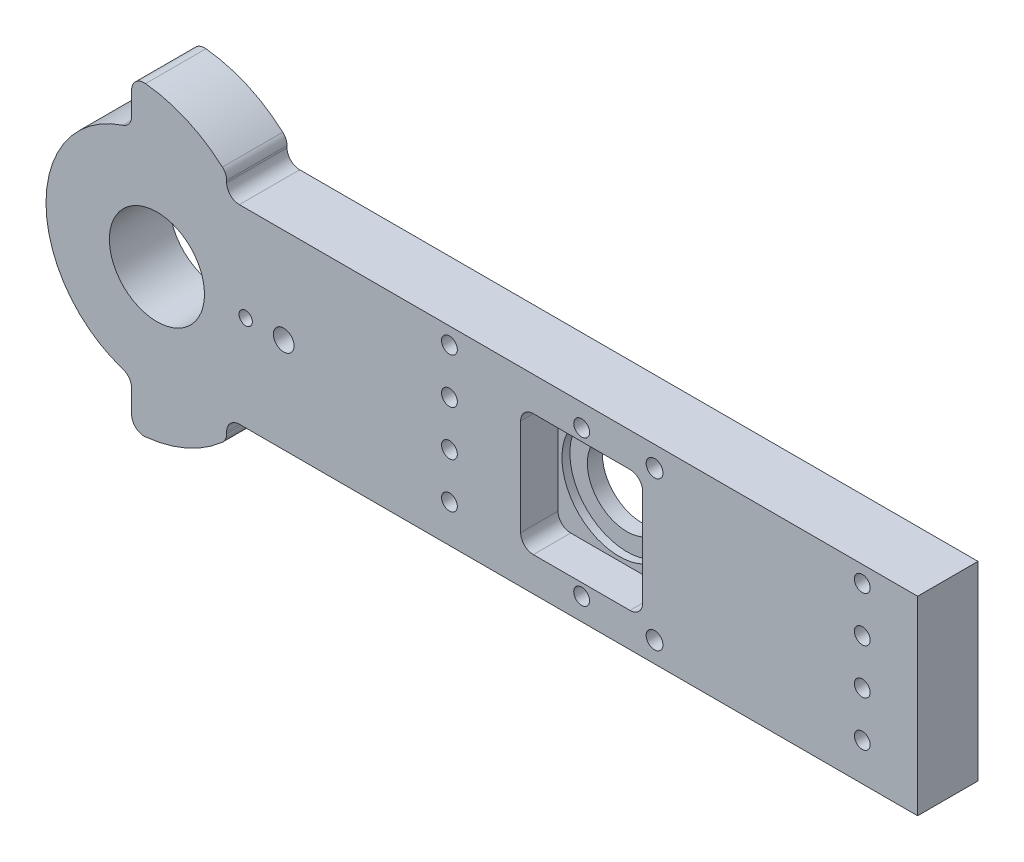
SolidWorks part; units mm, degrees
material "PE High Density"
ref_plane "Front Plane" through (0, 0, 0) normal (0, 0, 1) x (1, 0, 0)
ref_plane "Top Plane" through (0, 0, 0) normal (0, 1, 0) x (1, 0, 0)
ref_plane "Right Plane" through (0, 0, 0) normal (1, 0, 0) x (0, 0, -1)
sketch "Sketch1" plane through (0, 0, 0) normal (0, 0, 1) x (1, 0, 0)
  line L0 (30, 0) -> (30, 30) construction
  line L3 (0, 30) -> (18.0278, 30) construction
  line L6 (0, 0) -> (30, 0) construction
  line L8 (18.0278, 30) -> (240, 30)
  line L9 (240, 30) -> (240, -30)
  line L11 (18.0278, -30) -> (240, -30)
  circle A0 centre (0, 0) radius 30 construction
  arc A2 (18.0278, 30) -> (18.0278, -30) centre (0, 0) ccw
  circle A5 centre (0, 0) radius 9.525
  dimension "D1" = 60
  dimension "D4" = 70
  dimension "D8" = 19.05
  dimension "D2" = 240
extrude "Boss-Extrude1" add sketch "Sketch1" along normal mid plane 19.05
sketch "Sketch2" plane through (0, 0, -9.525) normal (0, 0, 1) x (1, 0, 0)
  line L0 (240, -30) -> (240, 30) construction
  circle A0 centre (134, 0) radius 12.5
  dimension "D2" = 25
  dimension "D1" = 106
extrude "Cut-Extrude1" cut sketch "Sketch2" along normal through all
sketch "Sketch3" plane through (0, 0, 9.525) normal (0, 0, 1) x (1, 0, 0)
  line L1 (114.5, -19.5) -> (153.5, -19.5) construction
  line L2 (114.5, -19.5) -> (114.5, 19.5) construction
  line L3 (114.5, 19.5) -> (153.5, 19.5) construction
  line L4 (153.5, -19.5) -> (153.5, 19.5) construction
  line L5 (114.5, -19.5) -> (153.5, 19.5) construction
  line L6 (114.5, 19.5) -> (153.5, -19.5) construction
  circle A0 centre (134, 0) radius 12.5 construction
  circle A3 centre (134, 0) radius 18
  dimension "D1" = 36
  dimension "D2" = 39
  dimension "D3" = 39
extrude "Cut-Extrude2" cut sketch "Sketch3" against normal blind 14.2875
sketch "Sketch4" plane through (0, 0, 9.525) normal (0, 0, 1) x (1, 0, 0)
  circle A0 centre (0, 0) radius 15
  dimension "D1" = 30
extrude "Cut-Extrude3" cut sketch "Sketch4" against normal through all
sketch "Sketch5" plane through (0, 0, 9.525) normal (0, 0, 1) x (1, 0, 0)
  line L1 (114.75, -19.25) -> (153.25, -19.25)
  line L2 (114.75, -19.25) -> (114.75, 19.25)
  line L3 (114.75, 19.25) -> (153.25, 19.25)
  line L4 (153.25, -19.25) -> (153.25, 19.25)
  line L5 (114.75, -19.25) -> (153.25, 19.25) construction
  line L6 (114.75, 19.25) -> (153.25, -19.25) construction
  point P0 (134, 0)
  dimension "D1" = 38.5
  dimension "D2" = 38.5
extrude "Cut-Extrude4" cut sketch "Sketch5" against normal offset from surface (11.7875 mm away) 2.5 up to face at (146.5, 0, -4.7625)
fillet "Fillet3" radius 4 4 edges at (153.25, -19.25, 3.6313) (114.75, -19.25, 3.6313) (153.25, 19.25, 3.6313) (114.75, 19.25, 3.6313)
sketch "Sketch12" plane through (0, 0, 9.525) normal (0, 0, 1) x (1, 0, 0)
  line L1 (240, 30) -> (18.0278, 30) construction
  line L3 (22, 30) -> (22, 36.35)
  line L4 (-8, 48.5) -> (22, 48.5) construction
  line L5 (-8, 48.5) -> (-8, 34.0735)
  line L6 (240, 30) -> (18.0278, 30) construction
  line L7 (22, 30) -> (18.0278, 30)
  arc A0 (-8, 48.5) -> (22, 36.35) centre (-8, 5.388) cw
  arc A1 (18.0278, 30) -> (18.0278, -30) centre (0, 0) ccw construction
  arc A2 (18.0278, 30) -> (-8, 34.0735) centre (0, 0) ccw
  dimension "D2" = 6.35
  dimension "D3" = 30
  dimension "D1" = 48.5
  dimension "D4" = 8
extrude "Boss-Extrude2" add sketch "Sketch12" against normal through all
mirror "Mirror4" about plane through (0, 0, 0) normal (0, 1, 0) of "Boss-Extrude2"
fillet "Fillet4" radius 4 6 edges at (22, 36.35, 0) (22, -36.35, 0) (-8, -48.5, 0) (-8, 48.5, 0) (-8, -34.0735, 0) (-8, 34.0735, 0)
fillet "Fillet6" radius 4 2 edges at (22, 30, 0) (22, -30, 0)
sketch "Sketch14" plane through (0, 0, 9.525) normal (0, 0, 1) x (1, 0, 0)
  line L0 (0, 0) -> (40, 0) construction
  line L1 (0, 0) -> (40, 0) construction
  circle A0 centre (0, 0) radius 40 construction
  circle A1 centre (40, 0) radius 3.2639
  dimension "D1" = 80
  dimension "D2" = 6.5278
  dimension "D3" = 0
extrude "Cut-Extrude6" cut sketch "Sketch14" against normal through all
sketch "Sketch15" plane through (0, 0, 9.525) normal (0, 0, 1) x (1, 0, 0)
  line L0 (134, 0) -> (134, 23) construction
  line L1 (240, 30) -> (26, 30) construction
  line L2 (134, 0) -> (146.5, 0) construction
  circle A0 centre (134, 0) radius 12.5 construction
  point P0 (134, 23)
  point P9 (134, -23)
  dimension "D1" = 7
hole_wizard "Ø5.0mm Dowel Hole1" positions "Sketch16" profile "Sketch17" hole size "Ø5.0" standard "ANSI Metric" end condition through all
sketch "Sketch16" plane through (0, 0, -9.525) normal (0, 0, -1) x (-1, 0, 0)
  point P0 (-134, 23)
  point P3 (-134, -23)
sketch "Sketch17" plane through (134, 23, -9.525) normal (1, 0, 0) x (0, 1, 0)
  line L0 (0, 0) -> (0, 19.05)
  line L1 (0, 19.05) -> (2.5, 19.05)
  line L2 (2.5, 19.05) -> (2.5, 0)
  line L5 (2.5, 0) -> (0, 0)
  line L11 (0, -6.35) -> (0, 107.95) construction
  dimension "Thru Hole Dia." = 5
  dimension "Thru Hole Depth" = 19.05
sketch "Sketch18" plane through (0, 0, 9.525) normal (0, 0, 1) x (1, 0, 0)
  line L0 (26, -30) -> (240, -30) construction
  line L1 (240, 30) -> (227.3, 30) construction
  line L2 (240, 30) -> (240, -30) construction
  line L3 (240, -30) -> (227.3, -30) construction
  line L4 (227.3, 30) -> (227.3, -30) construction
  line L5 (240, 30) -> (26, 30) construction
  line L6 (97.05, 30) -> (109.75, 30) construction
  line L7 (97.05, 30) -> (97.05, -30) construction
  line L8 (97.05, -30) -> (109.75, -30) construction
  line L9 (109.75, 30) -> (109.75, -30) construction
  line L10 (222.5375, 30) -> (222.5375, -30) construction
  line L11 (97.05, 30) -> (87.525, 30) construction
  line L12 (97.05, 30) -> (97.05, -30) construction
  line L13 (97.05, -30) -> (87.525, -30) construction
  line L14 (87.525, 30) -> (87.525, -30) construction
  line L15 (227.3, 30) -> (217.775, 30) construction
  line L16 (227.3, 30) -> (227.3, -30) construction
  line L17 (227.3, -30) -> (217.775, -30) construction
  line L18 (217.775, 30) -> (217.775, -30) construction
  line L19 (92.2875, 30) -> (92.2875, -30) construction
  line L20 (222.5375, -18.0938) -> (222.5375, -3.8063) construction
  point P21 (92.2875, -18.0938)
  point P22 (222.5375, -18.0938)
  point P24 (92.2875, -3.8063)
  point P25 (222.5375, -3.8063)
  point P26 (92.2875, 10.4812)
  point P27 (222.5375, 10.4812)
  point P28 (92.2875, 24.7687)
  point P29 (222.5375, 24.7687)
  dimension "D1" = 12.7
  dimension "D2" = 12.7
  dimension "D3" = 130.25
  dimension "D4" = 9.525
  dimension "D5" = 9.525
  dimension "D6" = 11.9062
  dimension "D8" = 14.2875
  dimension "D7" = 4
hole_wizard "CSK for #10 Flat Head Machine Screw1" positions "Sketch19" profile "Sketch20" countersink size "#10" standard "ANSI Inch" end condition up to next
sketch "Sketch19" plane through (0, 0, -9.525) normal (0, 0, -1) x (-1, 0, 0)
  point P0 (-92.2875, 24.7687)
  point P3 (-92.2875, 10.4812)
  point P6 (-92.2875, -3.8063)
  point P9 (-92.2875, -18.0938)
  point P12 (-222.5375, 24.7687)
  point P15 (-222.5375, 10.4812)
  point P18 (-222.5375, -3.8063)
  point P21 (-222.5375, -18.0938)
sketch "Sketch20" plane through (92.2875, 24.7687, -9.525) normal (1, 0, 0) x (0, 1, 0)
  line L0 (0, 0) -> (0, 19.05)
  line L1 (0, 19.05) -> (2.4892, 19.05)
  line L2 (2.4892, 19.05) -> (2.4892, 3.1265)
  line L3 (2.4892, 3.1265) -> (5.207, 0)
  line L5 (5.207, 0) -> (0, 0)
  line L6 (-2.4892, 3.1265) -> (-5.207, 0) construction
  line L11 (0, -6.35) -> (0, 107.95) construction
  dimension "Thru Hole Dia." = 4.9784
  dimension "Thru Hole Depth" = 19.05
  dimension "Near C'Sink Dia." = 10.414
  dimension "Near C'Sink Angle" = 82
sketch "Sketch21" plane through (0, 0, -9.525) normal (0, 0, -1) x (-1, 0, 0)
  line L0 (-240, -30) -> (-240, 30) construction
  line L1 (-240, 30) -> (-26, 30) construction
  line L2 (0, 0) -> (35, 0) construction
  arc A0 (10.7692, -33.302) -> (10.7692, 33.302) centre (0, 0) ccw construction
  point P0 (-157, 23.5)
  point P11 (-157, -23.5)
  dimension "D1" = 83
  dimension "D2" = 6.5
hole_wizard "CSK for M5 Flat Head Machine Screw1" positions "Sketch22" profile "Sketch23" countersink size "M5" standard "ANSI Metric" end condition through all
sketch "Sketch22" plane through (0, 0, -9.525) normal (0, 0, -1) x (-1, 0, 0)
  point P0 (-157, 23.5)
  point P3 (-157, -23.5)
sketch "Sketch23" plane through (157, 23.5, -9.525) normal (1, 0, 0) x (0, 1, 0)
  line L0 (0, 0) -> (0, 19.05)
  line L1 (0, 19.05) -> (2.65, 19.05)
  line L2 (2.65, 19.05) -> (2.65, 2.6)
  line L3 (2.65, 2.6) -> (5.25, 0)
  line L5 (5.25, 0) -> (0, 0)
  line L6 (-2.65, 2.6) -> (-5.25, 0) construction
  line L11 (0, -6.35) -> (0, 107.95) construction
  dimension "Thru Hole Dia." = 5.3
  dimension "Thru Hole Depth" = 19.05
  dimension "Near C'Sink Dia." = 10.5
  dimension "Near C'Sink Angle" = 90
sketch "Sketch24" plane through (0, 0, -9.525) normal (0, 0, -1) x (-1, 0, 0)
  point P0 (-28, 0)
  dimension "D1" = 28
hole_wizard "M5x0.8 Tapped Hole1" positions "Sketch25" profile "Sketch26" tap size "M5x0.8" standard "ANSI Metric" end condition through all
sketch "Sketch25" plane through (0, 0, -9.525) normal (0, 0, -1) x (-1, 0, 0)
  point P0 (-28, 0)
sketch "Sketch26" plane through (28, 0, -9.525) normal (1, 0, 0) x (0, 1, 0)
  line L0 (0, 0) -> (0, 19.05)
  line L1 (0, 19.05) -> (2.1, 19.05)
  line L2 (2.1, 19.05) -> (2.1, 0)
  line L5 (2.1, 0) -> (0, 0)
  line L11 (0, -6.35) -> (0, 107.95) construction
  dimension "Thru Tap Drill Dia." = 4.2
  dimension "Thru Tap Drill Depth" = 19.05
cosmetic thread "Hole Thread3" parameters "D2"=5
equation "\"D1@Boss-Extrude1\"=0.75in"
equation "\"D1@Sketch1\"=60"
equation "\"D1@Cut-Extrude2\"=8.000000mm+6.2875"
equation "\"D2@Sketch12\"=0.25in"
equation "\"D2@Sketch14\"=0.257in"
equation "\"D1@Sketch18\"=0.5in"
equation "\"D2@Sketch18\"=0.5in"
equation "\"D4@Sketch18\"=0.375in"
equation "\"D5@Sketch18\"=0.375in"
equation "\"D6@Sketch18\"=0.1875in + 0.5625in / 2"
equation "\"D1@Cut-Extrude3\"=0.375in"
equation "\"D8@Sketch1\"=0.75in"
